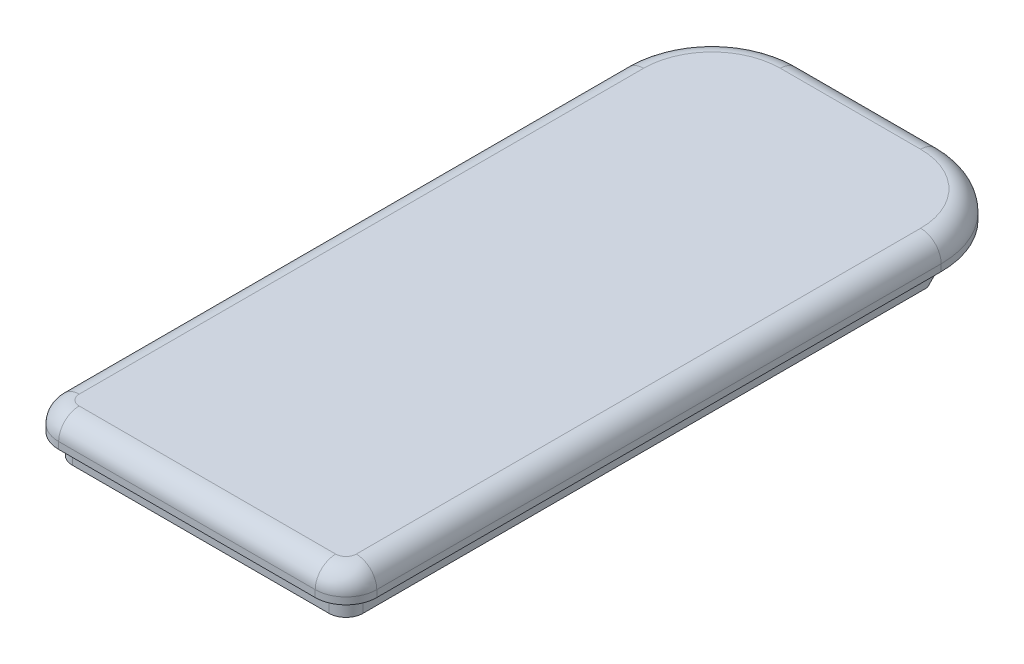
SolidWorks part; units mm, degrees
ref_plane "Спереди" through (0, 0, 0) normal (0, 0, 1) x (1, 0, 0)
ref_plane "Сверху" through (0, 0, 0) normal (0, 1, 0) x (1, 0, 0)
ref_plane "Справа" through (0, 0, 0) normal (1, 0, 0) x (0, 0, -1)
sketch "Эскиз1" plane through (0, 0, 0) normal (0, 1, 0) x (1, 0, 0)
  line L1 (4.5, 0) -> (42, 0)
  line L2 (0, 4.5) -> (0, 87)
  line L3 (13, 100) -> (33.5, 100)
  line L4 (46.5, 4.5) -> (46.5, 87)
  arc A0 (0, 4.5) -> (4.5, 0) centre (4.5, 4.5) ccw
  arc A1 (46.5, 4.5) -> (42, 0) centre (42, 4.5) cw
  arc A2 (33.5, 100) -> (46.5, 87) centre (33.5, 87) cw
  arc A3 (0, 87) -> (13, 100) centre (13, 87) cw
  point P7 (0, 0)
  point P10 (46.5, 0)
  point P15 (0, 100)
  dimension "D3" = 4.5
  dimension "D4" = 13
  dimension "D1" = 46.5
  dimension "D2" = 100
extrude "Бобышка-Вытянуть1" add sketch "Эскиз1" against normal blind 4
sketch "Эскиз2" plane through (0, -4, 0) normal (0, -1, 0) x (1, 0, 0)
  line L0 (3.5, -4.5) -> (3.5, -87)
  line L1 (13, -96.5) -> (33.5, -96.5)
  line L2 (43, -87) -> (43, -4.5)
  line L3 (42, -3.5) -> (4.5, -3.5)
  line L4 (0, -4.5) -> (0, -87)
  line L5 (13, -100) -> (33.5, -100)
  line L6 (46.5, -87) -> (46.5, -4.5)
  line L7 (42, 0) -> (4.5, 0)
  line L8 (0, -4.5) -> (0, -87) construction
  line L9 (13, -100) -> (33.5, -100) construction
  line L10 (46.5, -87) -> (46.5, -4.5) construction
  line L11 (42, 0) -> (4.5, 0) construction
  arc A0 (3.5, -87) -> (13, -96.5) centre (13, -87) ccw
  arc A1 (33.5, -96.5) -> (43, -87) centre (33.5, -87) ccw
  arc A2 (43, -4.5) -> (42, -3.5) centre (42, -4.5) ccw
  arc A3 (4.5, -3.5) -> (3.5, -4.5) centre (4.5, -4.5) ccw
  arc A4 (4.5, 0) -> (0, -4.5) centre (4.5, -4.5) ccw
  arc A5 (0, -87) -> (13, -100) centre (13, -87) ccw
  arc A6 (33.5, -100) -> (46.5, -87) centre (33.5, -87) ccw
  arc A7 (46.5, -4.5) -> (42, 0) centre (42, -4.5) ccw
  arc A8 (4.5, 0) -> (0, -4.5) centre (4.5, -4.5) ccw construction
  arc A9 (0, -87) -> (13, -100) centre (13, -87) ccw construction
  arc A10 (33.5, -100) -> (46.5, -87) centre (33.5, -87) ccw construction
  arc A11 (46.5, -4.5) -> (42, 0) centre (42, -4.5) ccw construction
  dimension "D1" = 0
  dimension "D2" = 3.5
extrude "Вырез-Вытянуть1" cut sketch "Эскиз2" against normal blind 1.5
sketch "Эскиз3" plane through (0, -4, 0) normal (0, -1, 0) x (-1, 0, 0)
  line L0 (-46.5, 4.5) -> (-46.5, 87) construction
  line L1 (-4.5, 0) -> (-42, 0) construction
  line L2 (0, 87) -> (0, 4.5) construction
  line L3 (-46.5, 4.5) -> (-46.5, 87) construction
  line L4 (-4.5, 0) -> (-42, 0) construction
  line L5 (0, 87) -> (0, 4.5) construction
  line L6 (-2, 87) -> (-2, 4.5)
  line L7 (-4.5, 2) -> (-42, 2)
  line L8 (-44.5, 4.5) -> (-44.5, 87)
  line L9 (-3.5, 87) -> (-3.5, 4.5)
  line L10 (-4.5, 3.5) -> (-42, 3.5)
  line L11 (-43, 4.5) -> (-43, 87)
  line L12 (-44.5, 87) -> (-43, 87)
  line L13 (-3.5, 87) -> (-2, 87)
  arc A0 (-46.5, 4.5) -> (-42, 0) centre (-42, 4.5) ccw construction
  arc A1 (-4.5, 0) -> (0, 4.5) centre (-4.5, 4.5) ccw construction
  arc A2 (-46.5, 4.5) -> (-42, 0) centre (-42, 4.5) ccw construction
  arc A3 (-4.5, 0) -> (0, 4.5) centre (-4.5, 4.5) ccw construction
  arc A4 (-4.5, 2) -> (-2, 4.5) centre (-4.5, 4.5) ccw
  arc A5 (-44.5, 4.5) -> (-42, 2) centre (-42, 4.5) ccw
  arc A6 (-4.5, 3.5) -> (-3.5, 4.5) centre (-4.5, 4.5) ccw
  arc A7 (-43, 4.5) -> (-42, 3.5) centre (-42, 4.5) ccw
  dimension "D1" = 2
  dimension "D2" = 1.5
extrude "Бобышка-Вытянуть2" add sketch "Эскиз3" along normal blind 3
chamfer "Фаска1" distance 3 angle 45 2 edges at (2.75, -4, -87) (43.75, -4, -87)
sketch "Эскиз4" plane through (0, -2.5, 0) normal (0, -1, 0) x (-1, 0, 0)
  line L0 (-23.25, 0) -> (-23.25, 17) construction
  line L2 (-23.25, 17) -> (-23.9, 17) construction
  line L3 (-23.9, 17) -> (-23.9, 17.65) construction
  line L4 (-23.9, 17.65) -> (-23.9, 19.5)
  line L5 (-23.9, 19.5) -> (-22.6, 19.5)
  line L6 (-22.6, 17.65) -> (-22.6, 19.5)
  line L7 (-22.6, 16.35) -> (-22.6, 14.5)
  line L8 (-23.9, 14.5) -> (-22.6, 14.5)
  line L9 (-23.9, 16.35) -> (-23.9, 14.5)
  line L10 (-23.9, 17.65) -> (-25.75, 17.65)
  line L11 (-25.75, 17.65) -> (-25.75, 16.35)
  line L12 (-23.9, 16.35) -> (-25.75, 16.35)
  line L13 (-22.6, 16.35) -> (-20.75, 16.35)
  line L14 (-20.75, 17.65) -> (-20.75, 16.35)
  line L15 (-22.6, 17.65) -> (-20.75, 17.65)
  line L16 (-4.5, 0) -> (-42, 0) construction
  point P10 (-23.25, 19.5)
  point P17 (-25.75, 17)
  dimension "D1" = 1.3
  dimension "D2" = 5
  dimension "D3" = 1.3
  dimension "D4" = 5
  dimension "D5" = 17
extrude "Бобышка-Вытянуть3" [suppressed] add sketch "Эскиз4" along normal blind 4.5
pattern_linear "Линейный массив1" [suppressed] count 2 spacing 43.5 count 2 spacing 7.5 of bodies 106
sketch "Эскиз5" plane through (0, -2.5, 0) normal (0, -1, 0) x (-1, 0, 0)
  line L0 (-23.25, 24) -> (-24, 24) construction
  line L2 (-23.25, 0) -> (-23.25, 24) construction
  line L3 (-4.5, 0) -> (-42, 0) construction
  line L4 (-22.5, 91) -> (-36.5, 91) construction
  line L5 (-24, 24) -> (-22.5, 24)
  line L6 (-24, 24) -> (-24, 91)
  line L7 (-24, 91) -> (-22.5, 91)
  line L8 (-22.5, 24) -> (-22.5, 91)
  line L9 (-36.5, 91) -> (-35, 91)
  line L10 (-36.5, 91) -> (-36.5, 18)
  line L11 (-36.5, 18) -> (-35, 18)
  line L12 (-35, 91) -> (-35, 18)
  dimension "D1" = 1.5
  dimension "D2" = 24
  dimension "D3" = 67
  dimension "D4" = 1.5
  dimension "D5" = 11
  dimension "D6" = 73
extrude "Бобышка-Вытянуть4" [suppressed] add sketch "Эскиз5" along normal blind 1.5
sketch "Эскиз6" plane through (0, -2.5, 0) normal (0, -1, 0) x (-1, 0, 0)
  line L1 (-32.5, 80.5) -> (-25.5, 80.5)
  line L2 (-32.5, 80.5) -> (-32.5, 82)
  line L3 (-32.5, 82) -> (-25.5, 82)
  line L4 (-25.5, 80.5) -> (-25.5, 82)
  line L5 (-33.5, 100) -> (-13, 100) construction
  line L6 (-46.5, 4.5) -> (-46.5, 87) construction
  dimension "D1" = 1.5
  dimension "D2" = 7
  dimension "D3" = 21
  dimension "D4" = 19.5
extrude "Бобышка-Вытянуть5" [suppressed] add sketch "Эскиз6" along normal blind 4.5
fillet "Скругление1" radius 3 8 edges at (1.318, 0, -1.318) (0, 0, -45.75) (3.8076, 0, -96.1924) (23.25, 0, -100) (42.6924, 0, -96.1924) (46.5, 0, -45.75) (45.182, 0, -1.318) (23.25, 0, 0)
